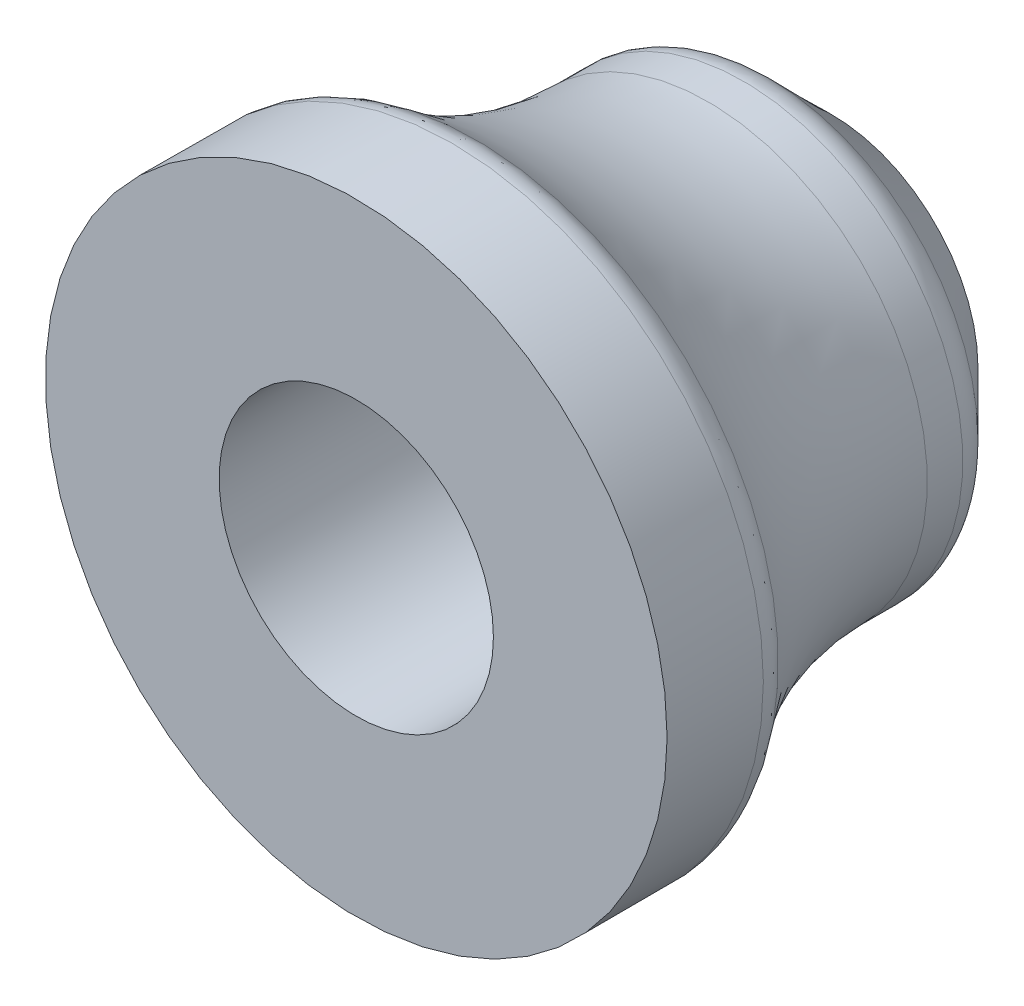
SolidWorks part; units mm, degrees
ref_plane "Plano frontal" through (0, 0, 0) normal (0, 0, 1) x (1, 0, 0)
ref_plane "Plano superior" through (0, 0, 0) normal (0, 1, 0) x (1, 0, 0)
ref_plane "Plano direito" through (0, 0, 0) normal (1, 0, 0) x (0, 0, -1)
sketch "Esboço1" plane through (0, 0, 0) normal (0, 0, 1) x (1, 0, 0)
  circle A0 centre (0, 0) radius 6
  dimension "D1" = 12
extrude "Ressalto-extrusão1" add sketch "Esboço1" along normal blind 13
sketch "Esboço2" plane through (0, 0, 13) normal (0, 0, 1) x (1, 0, 0)
  line L0 (-2.6833, 1.45) -> (2.6833, 1.45)
  circle A0 centre (0, 0) radius 3.05
  point P5 (0, -3.05)
  point P6 (0, 1.45)
  dimension "D1" = 6.1
  dimension "D2" = 4.5
extrude "Corte-extrusão1" cut sketch "Esboço2" against normal blind 12 contours L0 A0 region at (0, -0.5573, 13)
sketch "Esboço3" plane through (0, 0, 13) normal (0, 0, 1) x (1, 0, 0)
  circle A0 centre (0, 0) radius 3.75
  dimension "D1" = 7.5
extrude "Corte-extrusão2" cut sketch "Esboço3" against normal blind 10
chamfer "Chanfro1" distance 2 angle 45 1 edges at (6, 0, 0)
sketch "Esboço4" plane through (0, 0, 13) normal (0, 0, 1) x (1, 0, 0)
  circle A0 centre (0, 0) radius 3.75
  circle A1 centre (0, 0) radius 8.5
  circle A2 centre (0, 0) radius 3.75 construction
  dimension "D1" = 17
extrude "Ressalto-extrusão2" add sketch "Esboço4" against normal blind 3
fillet "Filete1" radius 10 1 edges at (6, 0, 10)
fillet "Filete3" radius 1 2 edges at (6, 0, 2) (8.5, 0, 10)
sketch "Esboço5" plane through (0, 0, 0) normal (0, 0, -1) x (-1, 0, 0)
  line L0 (-2.631, 3.0129) -> (-2.631, -3.0129)
  line L1 (-2.631, 3.0129) -> (-0.8756, 3.0129)
  line L2 (-0.8756, 3.0129) -> (-0.8756, 0.8777)
  line L6 (0.2069, 0) -> (2.5169, -3.0129)
  line L7 (2.5169, -3.0129) -> (0.7615, -3.0129)
  line L8 (0.7615, -3.0129) -> (-0.8756, -0.8777)
  line L9 (-0.8756, -0.8777) -> (-0.8756, -3.0129)
  line L10 (-0.8756, -3.0129) -> (-2.631, -3.0129)
  line L11 (-0.8756, 0.8777) -> (0.7615, 3.0129)
  line L12 (0.7615, 3.0129) -> (2.5169, 3.0129)
  line L13 (2.5169, 3.0129) -> (0.2069, 0)
  line L14 (-0.8756, -0.8777) -> (-0.8756, 0.8777) construction
  circle A1 centre (0, 0) radius 4 construction
  point P3 (-2.631, 0)
  point P12 (0, 0)
  point P13 (-0.8756, 0)
  point P14 (-1.0504, 0.1178)
  point P15 (0, 0)
  point P16 (-0.9106, 0.0736)
  point P17 (-2.375, 3.2186)
  point P18 (1.3412, 2.7964)
  point P19 (2.0403, -2.5756)
  point P20 (-1.3521, -0.5077)
  point P21 (0, 0)
  point P24 (0, 0)
  point P25 (0, 0)
  point P26 (0, 0)
extrude "Corte-extrusão3" cut sketch "Esboço5" against normal blind 0.2
